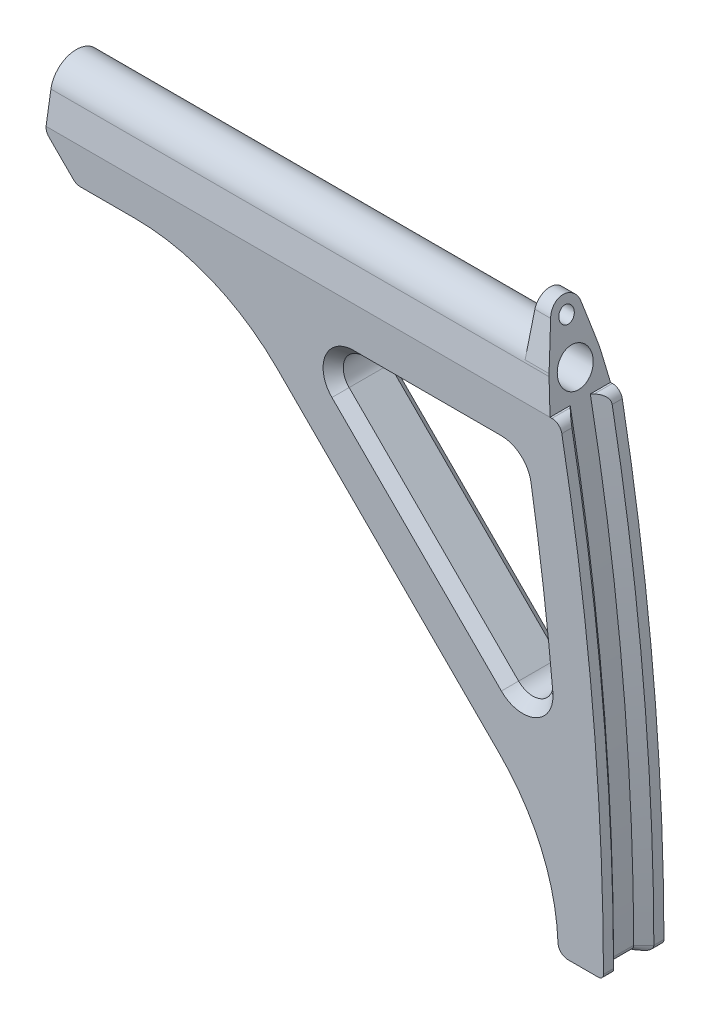
SolidWorks part; units mm, degrees
ref_plane "Front Plane" through (0, 0, 0) normal (0, 0, 1) x (1, 0, 0)
ref_plane "Top Plane" through (0, 0, 0) normal (0, 1, 0) x (1, 0, 0)
ref_plane "Right Plane" through (0, 0, 0) normal (1, 0, 0) x (0, 0, -1)
sketch "Sketch2" plane through (0, 0, 0) normal (0, 0, 1) x (1, 0, 0)
  line L0 (32.4563, 0) -> (32.4563, 45.72)
  line L1 (190.6962, 45.72) -> (240.6962, 45.72)
  line L2 (241.5, 0) -> (245, 0)
  line L3 (190.6962, 42.22) -> (237.7808, 42.22)
  line L4 (190.6962, 45.72) -> (190.6962, 42.22)
  line L5 (32.4563, 42.22) -> (240.6962, 42.22) construction
  line L6 (32.4563, 45.72) -> (240.6962, 45.72) construction
  arc A0 (245, 0) -> (240.6962, 45.72) centre (0, 0) ccw
  arc A1 (241.5, 0) -> (237.1327, 45.72) centre (0, 0) ccw
  circle A2 centre (0, 0) radius 245 construction
  circle A3 centre (0, 0) radius 241.5 construction
  dimension "D1" = 490
  dimension "D3" = 3.5
  dimension "D2" = 45.72
  dimension "D5" = 50
  dimension "D4" = 3.5
extrude "Boss-Extrude1" add sketch "Sketch2" along normal blind 4 contours A1 L2 A0 L1 | L3 A1 L1 L4
sketch "Sketch3" plane through (0, 0, 0) normal (0, 0, -1) x (-1, 0, 0)
  line L0 (-240.6962, 45.72) -> (-241.714, 45.72)
  line L1 (-245, 0) -> (-246, 0)
  line L5 (-237.7808, 42.22) -> (-190.6962, 42.22)
  line L6 (-190.6962, 42.22) -> (-190.6962, 45.72)
  line L7 (-190.6962, 45.72) -> (-240.6962, 45.72)
  line L8 (-245, 0) -> (-241.5, 0)
  line L9 (-237.7808, 42.22) -> (-190.6962, 42.22)
  line L10 (-190.6962, 42.22) -> (-190.6962, 45.72)
  line L11 (-190.6962, 45.72) -> (-240.6962, 45.72)
  line L12 (-245, 0) -> (-241.5, 0)
  arc A7 (-241.6787, 45.9066) -> (-246, 0) centre (0, 0) ccw
  arc A8 (-241.714, 45.72) -> (-246, 0) centre (0, 0) ccw
  arc A10 (-237.7808, 42.22) -> (-241.5, 0) centre (0, 0) ccw
  arc A11 (-240.6962, 45.72) -> (-245, 0) centre (0, 0) ccw
  arc A12 (-237.7808, 42.22) -> (-241.5, 0) centre (0, 0) ccw
  dimension "D2" = 0
  dimension "D1" = 1
extrude "Boss-Extrude2" add sketch "Sketch3" along normal blind 1
ref_plane "Plane1" through (0, 0, 2) normal (0, 0, 1) x (1, 0, 0)
mirror "Mirror1" about plane through (0, 0, 2) normal (0, 0, 1) of "Boss-Extrude2"
sketch "Sketch4" plane through (190.6962, 0, 0) normal (-1, 0, 0) x (0, 0, 1)
  line L1 (5, 45.72) -> (-1, 45.72) construction
  line L2 (5, 45.72) -> (-1, 45.72)
  line L3 (-1, 45.72) -> (0.0105, 51.9105)
  line L4 (5, 45.72) -> (3.9262, 52.2983)
  circle A0 centre (2, 48.27) radius 1.75
  circle A1 centre (2, 48.27) radius 2.55
  point P5 (2, 48.47)
  point P7 (2, 48.27)
  line M2 (5, 45.72) -> (-1, 45.72)
  dimension "D1" = 3.5
  dimension "D2" = 0.8
extrude "Boss-Extrude3" add sketch "Sketch4" against normal up to surface (50 mm away) contours A1 L3 L2 | A1 A0 | A1 L4 M2
fillet "Fillet1" radius 1 2 edges at (241.714, 45.72, -0.5) (241.714, 45.72, 4.5)
chamfer "Chamfer1" distance 30 angle 45 1 edges at (237.7808, 42.22, 2)
sketch "Sketch5" plane through (0, 0, -1) normal (0, 0, -1) x (-1, 0, 0)
  line L7 (-240.6962, 45.72) -> (-240.884, 45.72)
  line L8 (-246, 0) -> (-241.5, 0)
  line L9 (-241.3448, 8.656) -> (-207.7808, 42.22)
  line L10 (-207.7808, 42.22) -> (-190.6962, 42.22)
  line L11 (-190.6962, 42.22) -> (-190.6962, 45.72)
  line L12 (-190.6962, 45.72) -> (-240.6962, 45.72)
  line L13 (-240.6962, 45.72) -> (-240.884, 45.72)
  line L14 (-246, 0) -> (-241.5, 0)
  line L15 (-241.3448, 8.656) -> (-207.7808, 42.22)
  line L16 (-207.7808, 42.22) -> (-190.6962, 42.22)
  line L17 (-190.6962, 42.22) -> (-190.6962, 45.72)
  line L18 (-190.6962, 45.72) -> (-240.6962, 45.72)
  line L25 (-240.4243, 16.6476) -> (-216.3519, 40.72)
  line L26 (-216.3519, 40.72) -> (-237.535, 40.72)
  line L27 (-240.4243, 16.6476) -> (-216.3519, 40.72)
  line L28 (-216.3519, 40.72) -> (-237.535, 40.72)
  arc A3 (-240.884, 45.72) -> (-241.8672, 44.9025) centre (-240.884, 44.72) ccw
  arc A4 (-241.8672, 44.9025) -> (-246, 0) centre (0, 0) ccw
  arc A5 (-241.3448, 8.656) -> (-241.5, 0) centre (0, 0) ccw
  arc A6 (-240.884, 45.72) -> (-241.8672, 44.9025) centre (-240.884, 44.72) ccw
  arc A7 (-241.8672, 44.9025) -> (-246, 0) centre (0, 0) ccw
  arc A8 (-241.3448, 8.656) -> (-241.5, 0) centre (0, 0) ccw
  arc A12 (-237.535, 40.72) -> (-240.4243, 16.6476) centre (0, 0) ccw
  arc A13 (-237.535, 40.72) -> (-240.4243, 16.6476) centre (0, 0) ccw
  dimension "D1" = 0
  dimension "D2" = 5
extrude "Cut-Extrude1" cut sketch "Sketch5" against normal through all contours L28 A13 L27
fillet "Fillet3" radius 2 3 edges at (216.3519, 40.72, 2) (240.4243, 16.6476, 2) (237.535, 40.72, 2)
fillet "Fillet4" radius 20 2 edges at (241.3448, 8.656, 2) (207.7808, 42.22, 2)
chamfer "Chamfer2" distance 1 angle 45 12 edges at (237.1373, 40.2445, -1) (239.0512, 30.5861, -1) (228.5115, 40.72, -1) (238.8433, 20.0957, -1) (219.3326, 39.4854, -1) (228.1729, 28.899, -1) (237.1373, 40.2445, 5) (239.0512, 30.5861, 5) (228.5115, 40.72, 5) (238.8433, 20.0957, 5) (219.3326, 39.4854, 5) (228.1729, 28.899, 5)
fillet "Fillet5" radius 0.5 3 edges at (246, 0, -0.5) (245, 0, 2) (246, 0, 4.5)
ref_plane "Plane2" through (237.6962, 0, 0) normal (-1, 0, 0) x (0, 0, 1)
sketch "Sketch6" plane through (237.6962, 0, 0) normal (-1, 0, 0) x (0, 0, 1)
  line L0 (3.5032, 52.748) -> (5.8249, 43.5164)
  line L2 (-2.4696, 40.953) -> (0.4968, 52.748)
  line L7 (4, 0.501) -> (4, 45.72)
  line L8 (0, 0.501) -> (4, 0.501)
  line L9 (0, 45.72) -> (0, 0.501)
  line L10 (-1, 45.72) -> (0, 45.72)
  line L11 (-0.5167, 48.6808) -> (-1, 45.72)
  line L12 (5, 45.72) -> (4.5167, 48.6808)
  line L13 (4, 45.72) -> (5, 45.72)
  line L14 (4, 0.501) -> (4, 45.72)
  line L15 (0, 0.501) -> (4, 0.501)
  line L16 (0, 45.72) -> (0, 0.501)
  line L17 (-1, 45.72) -> (0, 45.72)
  line L18 (-0.5167, 48.6808) -> (-1, 45.72)
  line L19 (5, 45.72) -> (4.5167, 48.6808)
  line L20 (4, 45.72) -> (5, 45.72)
  circle A0 centre (2, 52.37) radius 0.75
  arc A1 (4.5167, 48.6808) -> (-0.5167, 48.6808) centre (2, 48.27) ccw
  arc A2 (4.5167, 48.6808) -> (-0.5167, 48.6808) centre (2, 48.27) ccw
  circle A3 centre (2, 52.37) radius 1.55
  point P12 (0, 0)
  point P15 (1.7436, 51.6662)
  dimension "D2" = 1.5
  dimension "D1" = 0
  dimension "D3" = 0.8
extrude "Boss-Extrude4" add sketch "Sketch6" against normal up to surface (2.3758 mm away) contours A3 L2 L18 A2 | A3 A0 | A3 A2 L0
fillet "Fillet6" radius 1 1 edges at (241.5, 0, 2)
chamfer "Chamfer3" distance 1 angle 45 4 edges at (244.8534, 0.1468, 4) (243.8981, 23.2105, 4) (244.8534, 0.1468, 0) (243.8981, 23.2105, 0)
chamfer "Chamfer4" distance 3 angle 45 1 edges at (190.6962, 42.22, 2)
fillet "Fillet7" radius 1 2 edges at (193.6962, 42.22, 2) (190.6962, 45.22, 2)
sketch "Sketch8" plane through (0, 0, -1) normal (0, 0, -1) x (-1, 0, 0)
  text T0 "<i>redline-  bagel</i>" font "Comfortaa" height 3
  text T1 "<i>winner</i>" font "Comfortaa" height 2
  point P1 (-228.1879, 43.151)
  point P2 (-227.1611, 42.6085)
  point P3 (-225.8553, 42.5546)
  point P4 (-223.866, 42.1743)
  point P5 (0, 0)
  point P7 (-209.9037, 42.2629)
  point P8 (0, 0)
  point P9 (0, 0)
extrude "Cut-Extrude2" cut sketch "Sketch8" against normal blind 0.5
